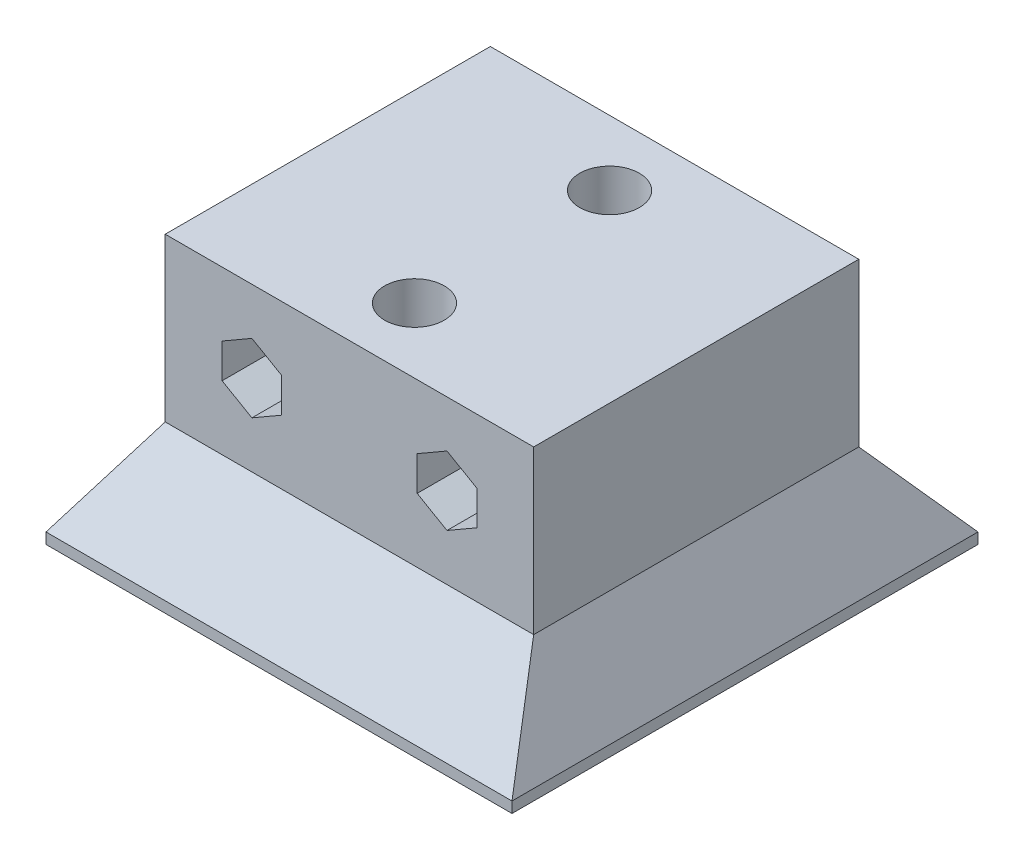
SolidWorks part; units mm, degrees
ref_plane "Front Plane" through (0, 0, 0) normal (0, 0, 1) x (1, 0, 0)
ref_plane "Top Plane" through (0, 0, 0) normal (0, 1, 0) x (1, 0, 0)
ref_plane "Right Plane" through (0, 0, 0) normal (1, 0, 0) x (0, 0, -1)
sketch "Sketch1" plane through (0, 0, 0) normal (0, 0, 1) x (1, 0, 0)
  line L1 (0, 0) -> (34, 0)
  line L2 (0, 0) -> (0, 15)
  line L3 (0, 15) -> (34, 15)
  line L4 (34, 0) -> (34, 15)
  dimension "D1" = 34
  dimension "D2" = 15
extrude "Boss-Extrude1" add sketch "Sketch1" along normal blind 30
sketch "Sketch3" plane through (0, 0, 30) normal (0, 0, 1) x (1, 0, 0)
  line L0 (0, 0) -> (-4.5, -7.7942)
  line L1 (-4.5, -8.7942) -> (38.5, -8.7942)
  line L2 (38.5, -7.7942) -> (34, 0)
  line L3 (0, 0) -> (34, 0) construction
  line L4 (0, 0) -> (34, 0)
  line L5 (-4.5, -7.7942) -> (-4.5, -8.7942)
  line L6 (38.5, -8.7942) -> (38.5, -7.7942)
  dimension "D1" = 120
  dimension "D2" = 120
  dimension "D3" = 43
  dimension "D4" = 1
extrude "Boss-Extrude2" add sketch "Sketch3" against normal blind 36.5 and the other way blind 6.5
sketch "Sketch5" plane through (0, 0, 30) normal (0, 0, 1) x (1, 0, 0)
  line L0 (34, 15) -> (0, 15) construction
  line L1 (8, 4.3246) -> (10.75, 5.9123)
  line L2 (10.75, 5.9123) -> (10.75, 9.0877)
  line L3 (10.75, 9.0877) -> (8, 10.6754)
  line L4 (8, 10.6754) -> (5.25, 9.0877)
  line L5 (5.25, 9.0877) -> (5.25, 5.9123)
  line L6 (5.25, 5.9123) -> (8, 4.3246)
  line L7 (26, 4.3246) -> (28.75, 5.9123)
  line L8 (28.75, 5.9123) -> (28.75, 9.0877)
  line L9 (28.75, 9.0877) -> (26, 10.6754)
  line L10 (26, 10.6754) -> (23.25, 9.0877)
  line L11 (23.25, 9.0877) -> (23.25, 5.9123)
  line L12 (23.25, 5.9123) -> (26, 4.3246)
  line L14 (0, 15) -> (0, 0) construction
  line L15 (34, 0) -> (34, 15) construction
  circle A0 centre (8, 7.5) radius 2.75 construction
  circle A1 centre (26, 7.5) radius 2.75 construction
  dimension "D1" = 7.5
  dimension "D2" = 7.5
  dimension "D3" = 8
  dimension "D4" = 5.5
  dimension "D5" = 5.5
  dimension "D6" = 8
extrude "Cut-Extrude2" cut sketch "Sketch5" against normal through all
sketch "Sketch6" plane through (0, 0, 0) normal (-1, 0, 0) x (0, 0, 1)
  line L0 (30, 0) -> (36.5, -7.7942)
  line L1 (36.5, -7.7942) -> (36.5, 0)
  line L2 (36.5, 0) -> (30, 0)
  line L3 (0, 0) -> (-6.5, -7.7942)
  line L4 (-6.5, -7.7942) -> (-6.5, 0)
  line L5 (-6.5, 0) -> (0, 0)
extrude "Cut-Extrude3" cut sketch "Sketch6" against normal through all and the other way through all
sketch "Sketch7" plane through (0, 15, 0) normal (0, 1, 0) x (1, 0, 0)
  line L0 (0, -30) -> (0, 0) construction
  line L1 (34, -30) -> (0, -30) construction
  line L2 (34, 0) -> (0, 0) construction
  circle A0 centre (17, -6) radius 2.75
  circle A1 centre (17, -24) radius 2.75
  point P8 (17, 0)
  dimension "D2" = 5.5
  dimension "D3" = 17
  dimension "D4" = 6
  dimension "D5" = 6
extrude "Cut-Extrude4" cut sketch "Sketch7" against normal through all
